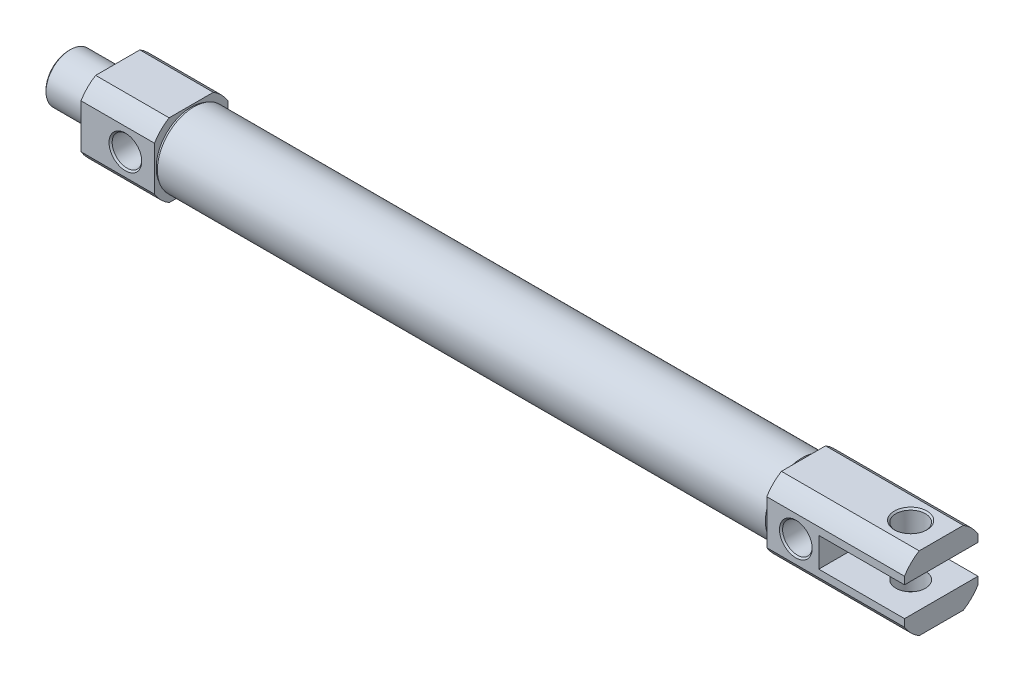
SolidWorks part; units mm, degrees
ref_plane "Front Plane" through (0, 0, 0) normal (0, 0, 1) x (1, 0, 0)
ref_plane "Top Plane" through (0, 0, 0) normal (0, 1, 0) x (1, 0, 0)
ref_plane "Right Plane" through (0, 0, 0) normal (1, 0, 0) x (0, 0, -1)
sketch "Sketch1" plane through (0, 0, 0) normal (1, 0, 0) x (0, 0, -1)
  circle A0 centre (0, 0) radius 5
  circle A1 centre (0, 0) radius 5.97
  dimension "D1" = 10
  dimension "D2" = 11.94
extrude "Boss-Extrude1" add sketch "Sketch1" along normal mid plane 80.4 contours A0 region at (0, 0, 0)
extrude "Boss-Extrude2" add sketch "Sketch1<3>" along normal mid plane 100
sketch "Sketch1<3>" plane through (0, 0, 0) normal (1, 0, 0) x (0, 0, -1) same geometry as "Sketch1"
chamfer "Chamfer1" distance 0.254 angle 60 1 edges at (50, 0, -5.97) first distance on face at (50, 0, -5.97)
chamfer "Chamfer2" distance 0.254 angle 60 1 edges at (-50, 0, -5.97) first distance on face at (-50, 0, -5.97)
sketch "Sketch2" plane through (50, 0, 0) normal (1, 0, 0) x (0, 0, -1)
  line L1 (6, -6) -> (-6, -6)
  line L2 (6, -6) -> (6, 6)
  line L3 (6, 6) -> (-6, 6)
  line L4 (-6, -6) -> (-6, 6)
  line L5 (6, -6) -> (-6, 6) construction
  line L6 (6, 6) -> (-6, -6) construction
  circle A0 centre (0, 0) radius 7
  point P0 (0, 0)
  dimension "D3" = 14
  dimension "D1" = 12
  dimension "D2" = 12
sketch "Sketch3" plane through (50, 0, 0) normal (1, 0, 0) x (0, 0, -1)
  line L0 (-6, 3.6055) -> (-6, -3.6055)
  line L1 (6, 3.6055) -> (6, -3.6055)
  line L2 (-3.6055, 6) -> (3.6055, 6)
  line L3 (-3.6055, -6) -> (3.6055, -6)
  line L4 (6, -6) -> (6, 6) construction
  line L5 (6, 6) -> (-6, 6) construction
  line L6 (-6, -6) -> (-6, 6) construction
  line L7 (6, -6) -> (-6, -6) construction
  arc A0 (-6, 3.6055) -> (-3.6055, 6) centre (0, 0) cw
  arc A1 (6, 3.6055) -> (3.6055, 6) centre (0, 0) ccw
  arc A2 (6, -3.6055) -> (3.6055, -6) centre (0, 0) cw
  arc A3 (-6, -3.6055) -> (-3.6055, -6) centre (0, 0) ccw
  circle A4 centre (0, 0) radius 7 construction
extrude "Boss-Extrude3" add sketch "Sketch3" along normal blind 22.5
sketch "Sketch5" plane through (0, 6, 0) normal (0, 1, 0) x (1, 0, 0)
  line L0 (72.5, 3.6055) -> (72.5, -3.6055) construction
  circle A0 centre (67.5, 0) radius 2.415
  dimension "D2" = 4.8301
  dimension "D1" = 5
extrude "Cut-Extrude2" cut sketch "Sketch5" against normal through all
sketch "Sketch6" plane through (0, 0, 6) normal (0, 0, 1) x (1, 0, 0)
  line L0 (72.5, 3.6055) -> (72.5, -3.6055) construction
  line L1 (58.5, -2.39) -> (72.5, -2.39)
  line L2 (58.5, -2.39) -> (58.5, 2.39)
  line L3 (58.5, 2.39) -> (72.5, 2.39)
  line L4 (72.5, -2.39) -> (72.5, 2.39)
  line L5 (58.5, -2.39) -> (72.5, 2.39) construction
  line L6 (58.5, 2.39) -> (72.5, -2.39) construction
  point P0 (65.5, 0)
  dimension "D1" = 14
  dimension "D2" = 4.78
extrude "Cut-Extrude3" cut sketch "Sketch6" against normal through all
extrude "Boss-Extrude4" add sketch "Sketch3<2>" against normal blind 12 from surface starting at face at (-50, 0, -5.716)
sketch "Sketch3<2>" plane through (50, 0, 0) normal (1, 0, 0) x (0, 0, -1) same geometry as "Sketch3"
sketch "Sketch4" plane through (0, 0, 6) normal (0, 0, 1) x (1, 0, 0)
  line L0 (50, 3.6055) -> (50, -3.6055) construction
  line L1 (-50, 3.6055) -> (-50, -3.6055) construction
  circle A0 centre (54.75, 0) radius 2.415
  circle A1 centre (-54.75, 0) radius 2.415
  dimension "D2" = 4.8301
  dimension "D1" = 4.75
  dimension "D3" = 4.75
extrude "Cut-Extrude4" cut sketch "Sketch4" against normal blind 6
sketch "Sketch8" plane through (-62, 0, 0) normal (-1, 0, 0) x (0, 0, 1)
  circle A0 centre (0, 0) radius 3.9688
  circle A1 centre (0, 0) radius 2.1827
  dimension "D1" = 4.3655
  dimension "D2" = 7.9375
extrude "Boss-Extrude5" add sketch "Sketch8" along normal blind 8
chamfer "Chamfer5" distance 0.254 angle 45 6 edges at (67.5, -6, 2.415) (67.5, 6, 2.415) (57.165, 0, 6) (-52.335, 0, 6) (-70, 0, 3.9688) (-70, 0, 2.1827)
equation "\"D2@Sketch2\"=\"D1@Sketch2\""
